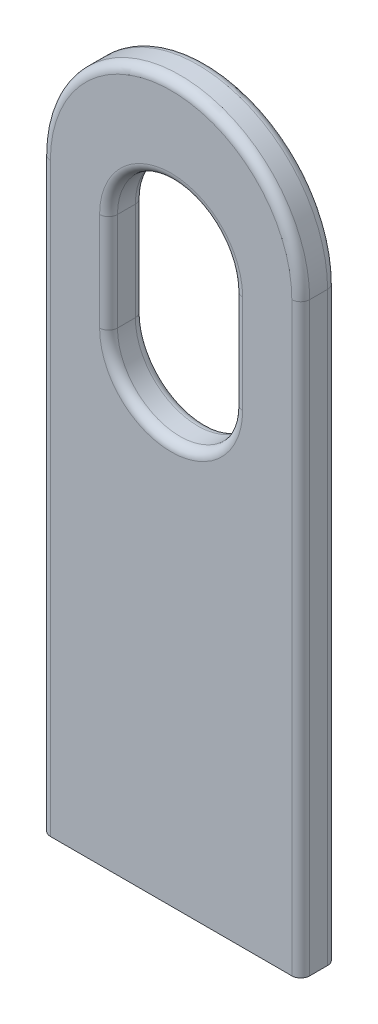
SolidWorks part; units mm, degrees
material "Brass"
ref_plane "Frontal" through (0, 0, 0) normal (0, 0, 1) x (1, 0, 0)
ref_plane "Superior" through (0, 0, 0) normal (0, 1, 0) x (1, 0, 0)
ref_plane "Direito" through (0, 0, 0) normal (1, 0, 0) x (0, 0, -1)
sketch "Sketch1" plane through (0, 0, 0) normal (0, 0, 1) x (1, 0, 0)
  line L0 (0, 7) -> (0, 8) construction
  line L1 (-1.45, 8) -> (1.45, 8)
  line L2 (-1.45, 8) -> (-1.45, 0)
  line L3 (-1.45, 0) -> (1.45, 0)
  line L4 (1.45, 8) -> (1.45, 0)
  line L5 (-0.7, 7) -> (0.7, 7)
  line L6 (-0.7, 7) -> (-0.7, 4.5)
  line L7 (-0.7, 4.5) -> (0.7, 4.5)
  line L8 (0.7, 7) -> (0.7, 4.5)
  dimension "D1" = 2.9
  dimension "D2" = 8
  dimension "D3" = 1.4
  dimension "D4" = 2.5
  dimension "D5" = 1
extrude "Extrude1" add sketch "Sketch1" along normal mid plane 0.4
fillet "Fillet4" 2 edges at (1.45, 8, 0) (-1.45, 8, 0) type full round first side face at (1.45, 4, 0) second side face at (-1.45, 4, 0) middle face at (0, 8, 0)
fillet "Fillet5" 2 edges at (-0.7, 7, 0) (0.7, 7, 0) type full round first side face at (-0.7, 5.75, 0) second side face at (0.7, 5.75, 0) middle face at (0, 7, 0)
fillet "Fillet6" 2 edges at (-0.7, 4.5, 0) (0.7, 4.5, 0) type full round first side face at (-0.7, 5.4, 0) second side face at (0.7, 5.4, 0) middle face at (0, 4.5, 0)
fillet "Fillet3" radius 0.1 14 edges at (-1.45, 3.275, -0.2) (-1.45, 3.275, 0.2) (1.45, 3.275, -0.2) (1.45, 3.275, 0.2) (0.7, 5.75, 0.2) (0.7, 5.75, -0.2) (-0.7, 5.75, 0.2) (-0.7, 5.75, -0.2) (0, 7, 0.2) (0, 4.5, 0.2) (0, 7, -0.2) (0, 4.5, -0.2) (0, 8, -0.2) (0, 8, 0.2)
